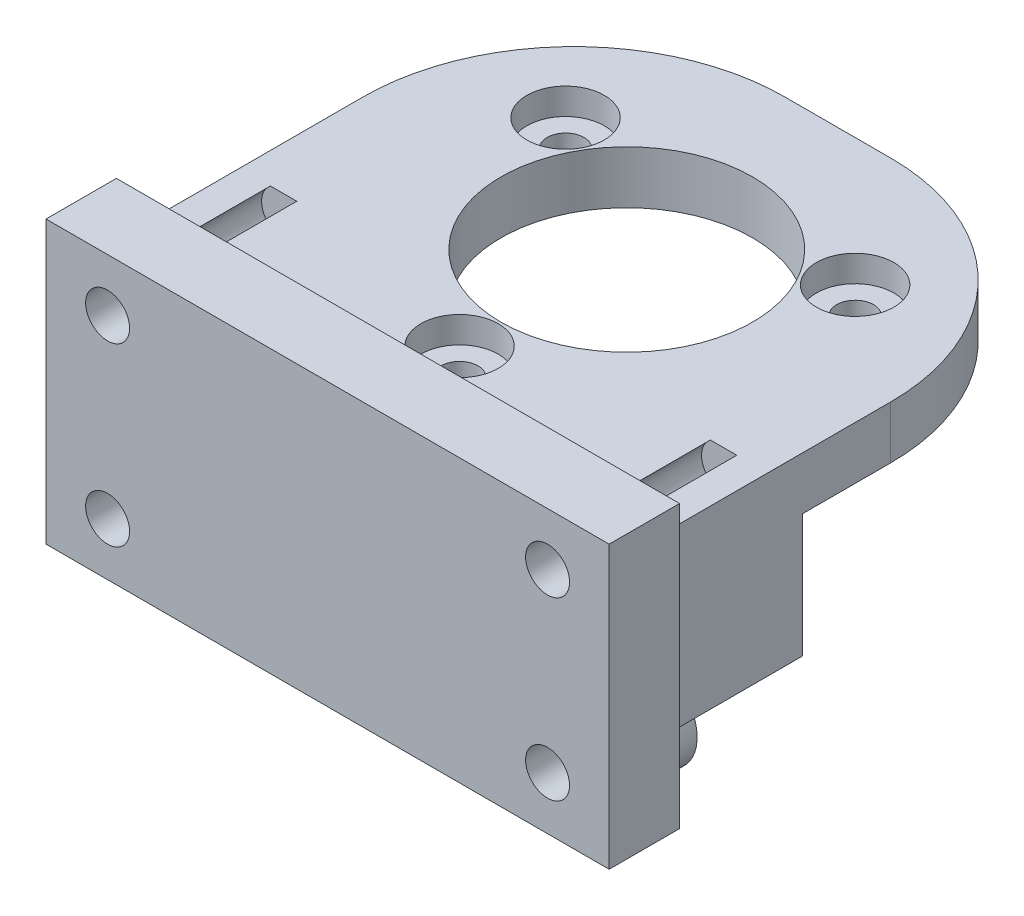
SolidWorks part; units mm, degrees
ref_plane "Front Plane" through (0, 0, 0) normal (0, 0, 1) x (1, 0, 0)
ref_plane "Top Plane" through (0, 0, 0) normal (0, 1, 0) x (1, 0, 0)
ref_plane "Right Plane" through (0, 0, 0) normal (1, 0, 0) x (0, 0, -1)
sketch "Sketch1" plane through (0, 0, 0) normal (0, 0, 1) x (1, 0, 0)
  line L1 (-15, -5) -> (15, -5)
  line L2 (-15, -5) -> (-15, 5)
  line L3 (-15, 5) -> (15, 5)
  line L4 (15, -5) -> (15, 5)
  line L5 (-15, -5) -> (15, 5) construction
  line L6 (-15, 5) -> (15, -5) construction
  point P0 (0, 0)
  point P11 (0, 0)
  point P13 (0, 0.5)
  dimension "D1" = 30
  dimension "D2" = 10
extrude "Main" add sketch "Sketch1" along normal blind 25
sketch "Sketch5" plane through (0, -5, 0) normal (0, -1, 0) x (-1, 0, 0)
  line L0 (0, -21.5) -> (-8.2272, -7.25) construction
  line L1 (-8.2272, -7.25) -> (8.2272, -7.25) construction
  line L2 (8.2272, -7.25) -> (0, -21.5) construction
  line L4 (15, 0) -> (-15, 0) construction
  circle A0 centre (0, -12) radius 9.5 construction
  circle A1 centre (0, -21.5) radius 1.05
  circle A2 centre (-8.2272, -7.25) radius 1.05
  circle A3 centre (8.2272, -7.25) radius 1.05
  circle A4 centre (0, -12) radius 7.15
  dimension "D1" = 19
  dimension "D2" = 2.1
  dimension "D4" = 14.3
  dimension "D3" = 12
extrude "MainAndFixHole" cut sketch "Sketch5" against normal through all
sketch "Sketch6" plane through (0, 5, 0) normal (0, -1, 0) x (-1, 0, 0)
  circle A0 centre (0, -21.5) radius 2.2
  circle A1 centre (-8.2272, -7.25) radius 2.2
  circle A2 centre (8.2272, -7.25) radius 2.2
  dimension "D1" = 4.4
extrude "CoderFixHole2" cut sketch "Sketch6" along normal blind 1.5
sketch "Sketch11" plane through (0, -5, 0) normal (0, 1, 0) x (1, 0, 0)
  line L0 (-15, 0) -> (15, 0)
  line L1 (15, 0) -> (15, -17)
  line L2 (15, -17) -> (10.9087, -17)
  line L3 (-15, 0) -> (-15, -17)
  line L4 (-15, -17) -> (-10.9087, -17)
  line L8 (-15, 0) -> (15, 0) construction
  line L9 (15, -25) -> (15, 0) construction
  arc A0 (10.9087, -17) -> (-10.9087, -17) centre (0, -12) cw
  circle A1 centre (0, -12) radius 7.15 construction
  dimension "D1" = 12
  dimension "D2" = 5
extrude "CoderHole2" cut sketch "Sketch11" along normal blind 7
sketch "Sketch10" plane through (0, 0, 25) normal (0, 0, 1) x (1, 0, 0)
  line L0 (-15, -5) -> (15, -5) construction
  line L1 (-16, -9) -> (16, -9)
  line L2 (-16, -9) -> (-16, 7)
  line L3 (-16, 7) -> (16, 7)
  line L4 (16, -9) -> (16, 7)
  line L6 (15, 5) -> (-15, 5) construction
  point P4 (0, -5)
  point P5 (0, -5)
  point P6 (0, 5)
  point P9 (0, 7)
  point P11 (0, 5)
  dimension "D1" = 16
  dimension "D2" = 32
  dimension "D3" = 2
extrude "Link" add sketch "Sketch10" along normal blind 4
sketch "Sketch8" plane through (0, 0, 29) normal (0, 0, 1) x (1, 0, 0)
  line L0 (16, -9) -> (16, 7) construction
  line L5 (16, 7) -> (-16, 7) construction
  circle A0 centre (12.5, 4) radius 1.25
  point P3 (16, -1)
  point P11 (0, 7)
  dimension "D3" = 2.5
  dimension "D1" = 3
  dimension "D2" = 12.5
  dimension "D4" = 8
extrude "VerticalHoles" cut sketch "Sketch8" against normal blind 10
pattern_linear "HoleLPattern1" count 2 spacing 25 along (-1, 0, 0) count 2 spacing 10 along (0, -1, 0) of "VerticalHoles"
sketch "Sketch13" plane through (0, 0, 25) normal (0, 0, -1) x (-1, 0, 0)
  line L3 (-12.5, -6) -> (12.5, -6) construction
  circle A0 centre (-12.5, -6) radius 2.5
  circle A1 centre (12.5, -6) radius 2.5
  circle A3 centre (-12.5, -6) radius 1.25 construction
  point P2 (0, -6)
  dimension "D3" = 5
extrude "LinkReinforcement" add sketch "Sketch13" along normal blind 2
fillet "Fillet6" radius 12 2 edges at (15, 3.5, 0) (-15, 3.5, 0)
